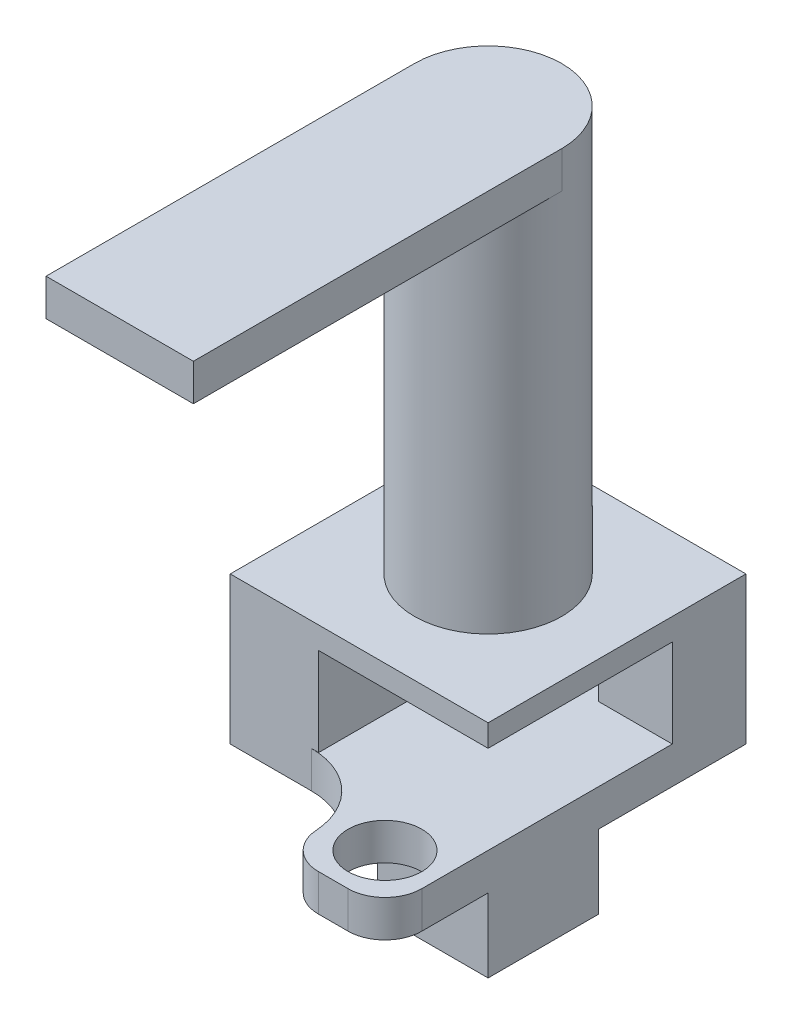
SolidWorks part; units mm, degrees
ref_plane "Front Plane" through (0, 0, 0) normal (0, 0, 1) x (1, 0, 0)
ref_plane "Top Plane" through (0, 0, 0) normal (0, 1, 0) x (1, 0, 0)
ref_plane "Right Plane" through (0, 0, 0) normal (1, 0, 0) x (0, 0, -1)
sketch "Sketch1" plane through (0, 0, 0) normal (0, 1, 0) x (1, 0, 0)
  line L2 (0, 0) -> (0, 35)
  line L10 (35, 35) -> (35, 0)
  line L11 (35, 35) -> (0, 35)
  line L13 (5.2825, 33.2179) -> (18.7064, 18.3923)
  line L15 (15, 15.0363) -> (1.5761, 29.8619)
  line L17 (35, 0) -> (35, -14)
  line L18 (35, -14) -> (21, -14)
  line L19 (21, -14) -> (21, 0)
  line L20 (21, 0) -> (0, 0)
  arc A2 (15, 15.0363) -> (18.7064, 18.3923) centre (16.8532, 16.7143) ccw
  arc A3 (5.2825, 33.2179) -> (1.5761, 29.8619) centre (3.4293, 31.5399) ccw
  circle A4 centre (28, -7) radius 5
  dimension "D3" = 10
  dimension "D4" = 14
  dimension "D7" = 7
  dimension "D8" = 7
  dimension "D1" = 35
  dimension "D2" = 35
  dimension "D5" = 5
  dimension "D6" = 20
  dimension "D9" = 14
extrude "Boss-Extrude1" add sketch "Sketch1" along normal blind 5
sketch "Sketch2" plane through (0, 0, 0) normal (0, -1, 0) x (1, 0, 0)
  line L3 (30, -5) -> (20, -5)
  line L4 (20, 0) -> (20, -5)
  line L7 (35, -15) -> (30, -15)
  line L8 (30, -5) -> (30, -15)
  line L20 (35, -15) -> (35, 0)
  line L21 (0, 0) -> (21, 0) construction
  line L22 (35, 0) -> (20, 0)
  line L23 (35, 14) -> (35, -35) construction
  dimension "D1" = 5
  dimension "D2" = 5
  dimension "D3" = 10
  dimension "D4" = 10
  dimension "D5" = 0
  dimension "D6" = 0
extrude "Boss-Extrude2" add sketch "Sketch2" along normal blind 10
sketch "Sketch3" plane through (0, 5, 0) normal (0, 1, 0) x (1, 0, 0)
  line L1 (0, 0) -> (12, 0)
  line L2 (0, 0) -> (0, 12)
  line L3 (0, 12) -> (12, 12)
  line L4 (12, 0) -> (12, 12)
  line L9 (35, 35) -> (25, 35)
  line L10 (35, 35) -> (35, 25)
  line L11 (35, 25) -> (25, 25)
  line L12 (25, 35) -> (25, 25)
  dimension "D1" = 12
  dimension "D3" = 10
extrude "Boss-Extrude3" add sketch "Sketch3" along normal blind 12
sketch "Sketch4" plane through (0, 17, 0) normal (0, 1, 0) x (1, 0, 0)
  line L1 (0, 0) -> (35, 0)
  line L2 (0, 0) -> (0, 35)
  line L3 (0, 35) -> (35, 35)
  line L4 (35, 0) -> (35, 35)
extrude "Boss-Extrude4" add sketch "Sketch4" along normal blind 3
sketch "Sketch5" plane through (0, 20, 0) normal (0, 1, 0) x (1, 0, 0)
  line L0 (0, 0) -> (35, 0) construction
  line L3 (0, 35) -> (0, 0) construction
  circle A0 centre (17.5, 17.5) radius 10
  dimension "D1" = 17.5
  dimension "D2" = 17.5
  dimension "D3" = 20
extrude "Boss-Extrude5" add sketch "Sketch5" along normal blind 50
sketch "Sketch6" plane through (0, 70, 0) normal (0, 1, 0) x (1, 0, 0)
  line L6 (7.5, 17.5) -> (7.5, -32.5)
  line L7 (7.5, -32.5) -> (27.5, -32.5)
  line L8 (27.5, 17.5) -> (27.5, -32.5)
  arc A1 (27.5, 17.5) -> (7.5, 17.5) centre (17.5, 17.5) ccw
  dimension "D1" = 50
extrude "Boss-Extrude6" add sketch "Sketch6" along normal blind 5
fillet "Fillet1" radius 10 1 edges at (21, 2.5, 0)
fillet "Fillet4" radius 5 2 edges at (35, 2.5, 14) (21, 2.5, 14)
